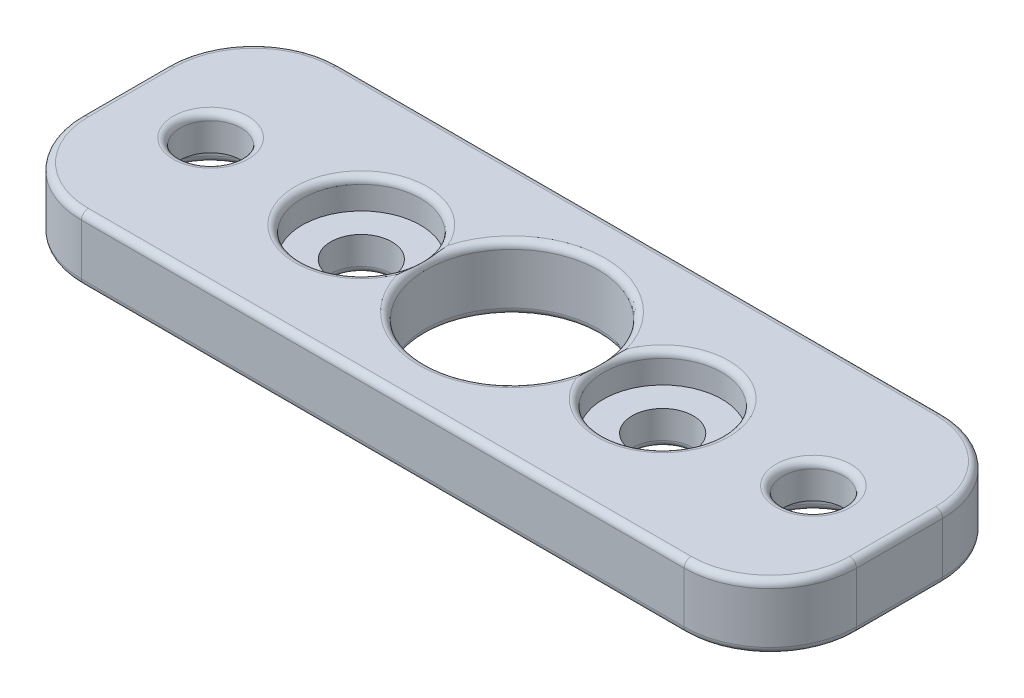
SolidWorks part; units mm, degrees
ref_plane "Front Plane" through (0, 0, 0) normal (0, 0, 1) x (1, 0, 0)
ref_plane "Top Plane" through (0, 0, 0) normal (0, 1, 0) x (1, 0, 0)
ref_plane "Right Plane" through (0, 0, 0) normal (1, 0, 0) x (0, 0, -1)
sketch "Sketch1" plane through (0, 0, 0) normal (0, 1, 0) x (1, 0, 0)
  line L1 (-28.575, -9.525) -> (28.575, -9.525)
  line L2 (-28.575, -9.525) -> (-28.575, 9.525)
  line L3 (-28.575, 9.525) -> (28.575, 9.525)
  line L4 (28.575, -9.525) -> (28.575, 9.525)
  line L5 (-28.575, -9.525) -> (28.575, 9.525) construction
  line L6 (-28.575, 9.525) -> (28.575, -9.525) construction
  circle A0 centre (0, 0) radius 6.35
  point P0 (0, 0)
  dimension "D3" = 12.7
  dimension "D1" = 57.15
  dimension "D2" = 19.05
extrude "Boss-Extrude1" add sketch "Sketch1" along normal blind 4.7625
sketch "Sketch2" plane through (0, 4.7625, 0) normal (0, 1, 0) x (1, 0, 0)
  point P0 (-11.1125, 0)
  point P1 (11.1125, 0)
  dimension "D1" = 22.225
  dimension "D2" = 11.1125
hole_wizard "CBORE for #8 Button Head Cap Screw1" positions "Sketch2" profile "Sketch4" counterbore size "#8" standard "ANSI Inch" end condition through all
sketch "Sketch4" plane through (-11.1125, 4.7625, 0) normal (1, 0, 0) x (0, 0, 1)
  line L0 (0, 0) -> (0, 4.7625)
  line L1 (0, 4.7625) -> (2.2479, 4.7625)
  line L3 (2.2479, 4.7625) -> (2.2479, 2.2098)
  line L4 (2.2479, 2.2098) -> (4.3663, 2.2098)
  line L5 (4.3663, 2.2098) -> (4.3663, 0)
  line L7 (4.3663, 0) -> (0, 0)
  line L11 (0, -6.35) -> (0, 107.95) construction
  dimension "Thru Hole Dia." = 4.4958
  dimension "Thru Hole Depth" = 4.7625
  dimension "C'Bore Dia." = 8.7325
  dimension "C'Bore Depth" = 2.2098
sketch "Sketch5" plane through (0, 0, 0) normal (0, -1, 0) x (-1, 0, 0)
  point P0 (22.225, 0)
  point P1 (-22.225, 0)
  dimension "D1" = 44.45
  dimension "D2" = 22.225
hole_wizard "CBORE for #8 Button Head Cap Screw2" positions "Sketch5" profile "Sketch6" counterbore size "#8" standard "ANSI Inch" end condition through all
sketch "Sketch6" plane through (-22.225, 0, 0) normal (1, 0, 0) x (0, 0, -1)
  line L0 (0, 0) -> (0, 4.7625)
  line L1 (0, 4.7625) -> (2.2479, 4.7625)
  line L3 (2.2479, 4.7625) -> (2.2479, 2.2098)
  line L4 (2.2479, 2.2098) -> (4.3663, 2.2098)
  line L5 (4.3663, 2.2098) -> (4.3663, 0)
  line L7 (4.3663, 0) -> (0, 0)
  line L11 (0, -6.35) -> (0, 107.95) construction
  dimension "Thru Hole Dia." = 4.4958
  dimension "Thru Hole Depth" = 4.7625
  dimension "C'Bore Dia." = 8.7325
  dimension "C'Bore Depth" = 2.2098
fillet "Fillet1" radius 6.35 4 edges at (28.575, 2.3813, -9.525) (28.575, 2.3813, 9.525) (-28.575, 2.3813, -9.525) (-28.575, 2.3813, 9.525)
fillet "Fillet2" radius 0.508 26 edges at (0, 4.7625, 9.525) (-26.7151, 4.7625, 7.6651) (-26.7151, 4.7625, -7.6651) (0, 4.7625, -9.525) (26.7151, 4.7625, -7.6651) (26.7151, 4.7625, 7.6651) (11.1125, 4.7625, 4.3663) (-11.1125, 4.7625, 4.3663) (22.225, 4.7625, -2.2479) (-22.225, 4.7625, -2.2479) (-26.7151, 0, -7.6651) (-26.7151, 0, 7.6651) (0, 0, 9.525) (26.7151, 0, 7.6651) (26.7151, 0, -7.6651) (0, 0, -9.525) (11.1125, 0, 2.2479) (-11.1125, 0, 2.2479) (22.225, 0, -4.3663) (-22.225, 0, -4.3663) (0, 4.7625, 6.35) (-28.575, 4.7625, 0) (28.575, 4.7625, 0) (-28.575, 0, 0) (28.575, 0, 0) (0, 0, 6.35)
